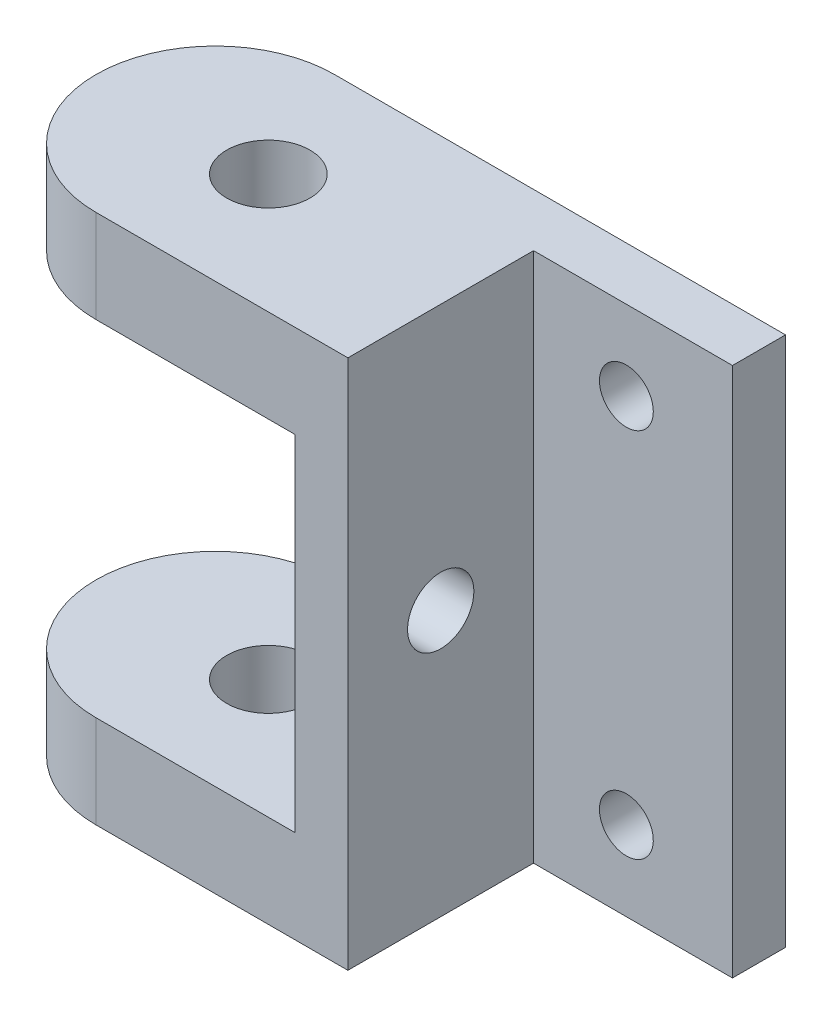
SolidWorks part; units mm, degrees
ref_plane "Alzado" through (0, 0, 0) normal (0, 0, 1) x (1, 0, 0)
ref_plane "Planta" through (0, 0, 0) normal (0, 1, 0) x (1, 0, 0)
ref_plane "Vista lateral" through (0, 0, 0) normal (1, 0, 0) x (0, 0, -1)
sketch "Croquis1" plane through (0, 0, 0) normal (1, 0, 0) x (0, 0, -1)
  line L0 (0.9, 2) -> (0.9, 1.3)
  line L1 (-0.9, 2) -> (0.9, 2)
  line L2 (-0.9, 2) -> (-0.9, -2)
  line L3 (-0.9, -2) -> (0.9, -2)
  line L4 (0.9, 2) -> (0.9, -2)
  line L5 (-0.9, 2) -> (0.9, -2) construction
  line L6 (-0.9, -2) -> (0.9, 2) construction
  line L7 (0.9, 2) -> (0.5, 2)
  line L8 (0.9, 2) -> (0.9, -2)
  line L9 (0.9, -2) -> (0.5, -2)
  line L10 (0.5, 2) -> (0.5, -2)
  line L11 (0.9, 1.3) -> (-0.9, 1.3)
  line L12 (-0.9, 1.3) -> (-0.9, 2)
  line L13 (-0.9, 2) -> (0.9, 2)
  line L14 (0.9, 2) -> (0.9, 1.3)
  line L15 (0.9, -2) -> (0.9, -1.3)
  line L16 (0.9, -1.3) -> (-0.9, -1.3)
  line L17 (-0.9, -1.3) -> (-0.9, -2)
  line L18 (-0.9, -2) -> (0.9, -2)
  point P0 (0, 0)
  dimension "D1" = 4
  dimension "D2" = 1.8
extrude "Saliente-Extruir1" add sketch "Croquis1" along normal blind 0.4 contours L16 L10 L11 L2 region at (0, 0, 0.2)
extrude "Saliente-Extruir2" add sketch "Croquis1<3>" along normal blind 1.9 contours L16 L4 L11 L10 region at (0, 0, -0.7)
sketch "Croquis1<3>" plane through (0, 0, 0) normal (1, 0, 0) x (0, 0, -1) same geometry as "Croquis1"
extrude "Saliente-Extruir3" add sketch "Croquis1<6>" along normal blind 1.9 contours L11 L0 L1 L10 region at (0, 1.65, -0.7)
sketch "Croquis1<6>" plane through (0, 0, 0) normal (1, 0, 0) x (0, 0, -1) same geometry as "Croquis1"
extrude "Saliente-Extruir5" add sketch "Croquis1<8>" along normal blind 0.4 contours L11 L10 L1 L2 region at (0, 1.65, 0.2)
sketch "Croquis1<8>" plane through (0, 0, 0) normal (1, 0, 0) x (0, 0, -1) same geometry as "Croquis1"
extrude "Saliente-Extruir6" add sketch "Croquis1<9>" along normal blind 0.4 contours L10 L16 L2 L3 region at (0, -1.65, 0.2)
sketch "Croquis1<9>" plane through (0, 0, 0) normal (1, 0, 0) x (0, 0, -1) same geometry as "Croquis1"
extrude "Saliente-Extruir7" add sketch "Croquis1<10>" along normal blind 1.9 contours L8 L16 L10 L3 region at (0, -1.65, -0.7)
sketch "Croquis1<10>" plane through (0, 0, 0) normal (1, 0, 0) x (0, 0, -1) same geometry as "Croquis1"
extrude "Saliente-Extruir8" add sketch "Croquis1<11>" against normal blind 2.4 contours L11 L0 L1 L10 | L11 L10 L1 L2 | L10 L16 L2 L3 | L8 L16 L10 L3 region at (0, 1.65, -0.7) region at (0, 1.65, 0.2) region at (0, -1.65, -0.7) region at (0, -1.65, 0.2)
sketch "Croquis1<11>" plane through (0, 0, 0) normal (1, 0, 0) x (0, 0, -1) same geometry as "Croquis1"
sketch "Croquis2" plane through (0, 0, -0.5) normal (0, 0, 1) x (1, 0, 0)
  line L0 (1.9, 2) -> (0.4, 2) construction
  line L2 (0.4, 2) -> (0.4, -2) construction
  line L3 (1.9, 0) -> (0.4, 0) construction
  line L4 (1.9, 2) -> (1.9, -2) construction
  circle A0 centre (1.1, 1.4) radius 0.203
  circle A1 centre (1.1, -1.4) radius 0.203
  dimension "D1" = 0.6
  dimension "D2" = 0.7
extrude "Cortar-Extruir1" cut sketch "Croquis2" against normal blind 2.4
sketch "Croquis3" plane through (0.4, 0, 0) normal (1, 0, 0) x (0, 0, -1)
  line L0 (-0.9, -2) -> (0.5, -2) construction
  line L1 (-0.9, 2) -> (-0.9, -2) construction
  circle A0 centre (-0.2, 0) radius 0.25
  point P2 (-0.2, -2)
  dimension "D1" = 2
  dimension "D2" = 0.7
extrude "Cortar-Extruir2" cut sketch "Croquis3" against normal blind 2.4
sketch "Croquis4" plane through (0, -2, 0) normal (0, -1, 0) x (1, 0, 0)
  line L0 (0.4, 0.9) -> (0.4, -0.5) construction
  circle A0 centre (-1.1, 0) radius 0.314
  dimension "D1" = 1.5
extrude "Cortar-Extruir3" cut sketch "Croquis4" against normal blind 10
fillet "Redondeo3" radius 0.9 2 edges at (-2.4, 1.65, 0.9) (-2.4, -1.65, 0.9)
fillet "Redondeo4" radius 0.9 2 edges at (-2.4, -1.65, -0.9) (-2.4, 1.65, -0.9)
